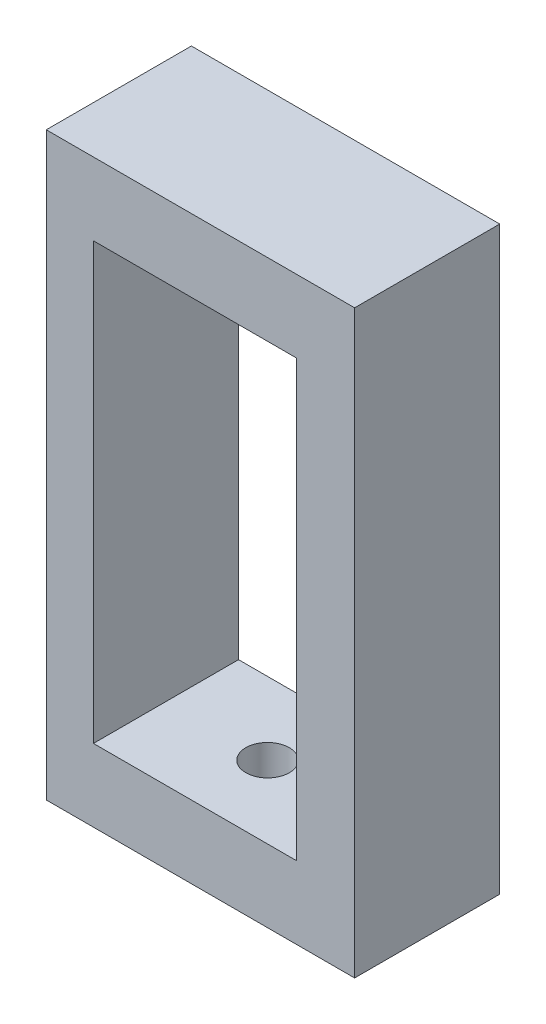
SolidWorks part; units mm, degrees
material "Brass"
ref_plane "Front Plane" through (0, 0, 0) normal (0, 0, 1) x (1, 0, 0)
ref_plane "Top Plane" through (0, 0, 0) normal (0, 1, 0) x (1, 0, 0)
ref_plane "Right Plane" through (0, 0, 0) normal (1, 0, 0) x (0, 0, -1)
sketch "Sketch1" plane through (0, 0, 0) normal (0, 0, 1) x (1, 0, 0)
  line L0 (0.75, 0) -> (22, 0)
  line L1 (22, 0) -> (22, 40)
  line L2 (22, 40) -> (0.75, 40)
  line L3 (0.75, 40) -> (0.75, 0)
  line L4 (4, 5) -> (18, 5)
  line L5 (18, 5) -> (18, 35)
  line L6 (18, 35) -> (4, 35)
  line L7 (4, 35) -> (4, 5)
extrude "Boss-Extrude1" add sketch "Sketch1" along normal blind 10
sketch "Sketch2" plane through (0, 0, 0) normal (0, 1, 0) x (1, 0, 0)
  circle A0 centre (11, -5) radius 1.5
  dimension "D1" = 3
extrude "Cut-Extrude1" cut sketch "Sketch2" against normal mid plane 30
